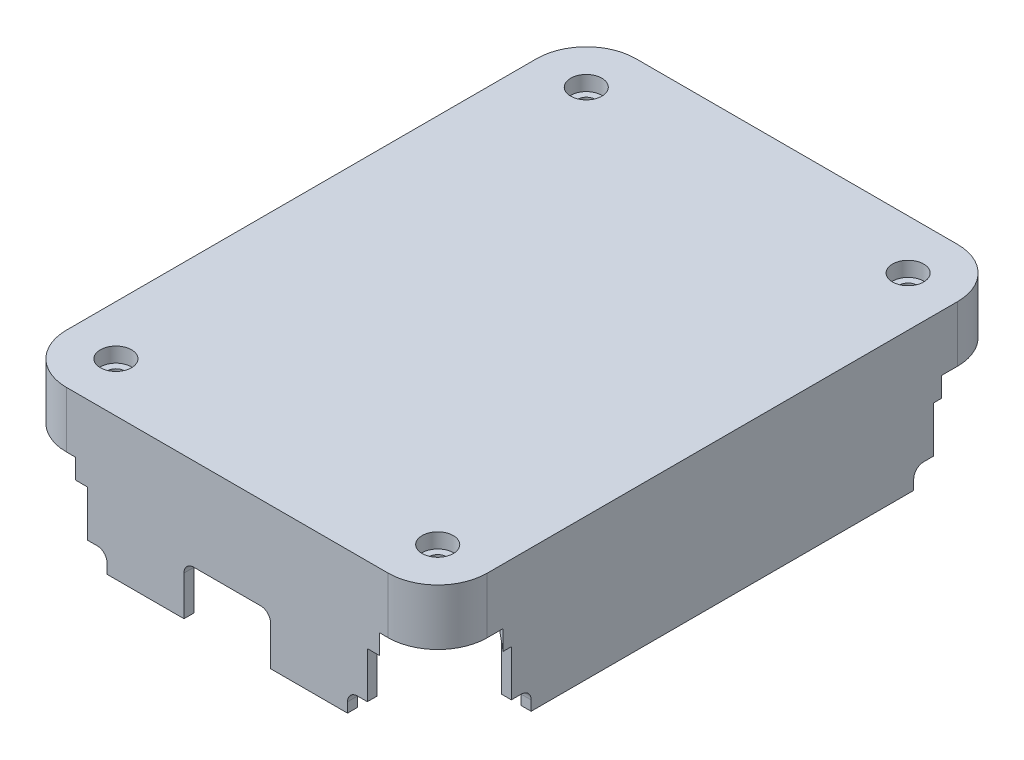
SolidWorks part; units mm, degrees
note: '?' marks a value the reader was unsure of.
material "3-D Printed ABS"
ref_plane "Front Plane" through (0, 0, 0) normal (0, 0, 1) x (1, 0, 0)
ref_plane "Top Plane" through (0, 0, 0) normal (0, 1, 0) x (1, 0, 0)
ref_plane "Right Plane" through (0, 0, 0) normal (1, 0, 0) x (0, 0, -1)
sketch "Sketch1" plane through (0, 0, 0) normal (0, 1, 0) x (1, 0, 0)
  line L1 (-53.975, -73.025) -> (53.975, -73.025)
  line L2 (-53.975, -73.025) -> (-53.975, 73.025)
  line L3 (-53.975, 73.025) -> (53.975, 73.025)
  line L4 (53.975, -73.025) -> (53.975, 73.025)
  line L5 (-53.975, -73.025) -> (53.975, 73.025) construction
  line L6 (-53.975, 73.025) -> (53.975, -73.025) construction
  point P0 (0, 0)
  dimension "D1" = 107.95
  dimension "D2" = 146.05
extrude "Boss-Extrude1" add sketch "Sketch1" against normal blind 2.54
sketch "Sketch13" plane through (0, 0, 0) normal (0, 1, 0) x (1, 0, 0)
  line L0 (0, 155.0212) -> (0, -155.0212) construction
  line L1 (0, 0) -> (-92.0171, 0) construction
  line L2 (53.975, -73.025) -> (53.975, 73.025) construction
  line L3 (53.975, -73.025) -> (28.575, -73.025)
  line L4 (53.975, -73.025) -> (53.975, -47.625)
  line L5 (53.975, -47.625) -> (28.575, -47.625)
  line L6 (28.575, -73.025) -> (28.575, -47.625)
  line L7 (-53.975, -73.025) -> (53.975, -73.025) construction
  line L8 (-28.575, -73.025) -> (-28.575, -47.625)
  line L9 (-53.975, -47.625) -> (-28.575, -47.625)
  line L10 (-53.975, -73.025) -> (-53.975, -47.625)
  line L11 (-53.975, -73.025) -> (-28.575, -73.025)
  line L12 (-53.975, 73.025) -> (-28.575, 73.025)
  line L13 (-53.975, 73.025) -> (-53.975, 47.625)
  line L14 (-53.975, 47.625) -> (-28.575, 47.625)
  line L15 (-28.575, 73.025) -> (-28.575, 47.625)
  line L16 (28.575, 73.025) -> (28.575, 47.625)
  line L17 (53.975, 47.625) -> (28.575, 47.625)
  line L18 (53.975, 73.025) -> (53.975, 47.625)
  line L19 (53.975, 73.025) -> (28.575, 73.025)
  dimension "D1" = 25.4
  dimension "D2" = 25.4
extrude "Boss-Extrude4" add sketch "Sketch13" against normal blind 19.431
sketch "Sketch2" plane through (0, 0, 0) normal (0, 1, 0) x (1, 0, 0)
  line L0 (0, 0) -> (100.1618, 0) construction
  line L1 (0, 0) -> (0, 86.3534) construction
  line L2 (-53.975, 73.025) -> (-53.975, -73.025) construction
  line L3 (53.975, 73.025) -> (-53.975, 73.025) construction
  line L4 (0, 0) -> (-53.975, 73.025) construction
  circle A0 centre (-41.275, 60.325) radius 3.302
  circle A1 centre (41.275, 60.325) radius 3.302
  circle A2 centre (41.275, -60.325) radius 3.302
  circle A3 centre (-41.275, -60.325) radius 3.302
  dimension "D1" = 6.604
  dimension "D3" = 12.7
  dimension "D2" = 12.7
extrude "Cut-Extrude1" cut sketch "Sketch2" against normal through all
sketch "Sketch3" plane through (0, 0, 0) normal (0, 1, 0) x (1, 0, 0)
  line L0 (-53.975, 25.4) -> (53.975, 25.4) construction
  line L1 (-23.495, 60.325) -> (-19.05, 60.325)
  line L2 (-23.495, 60.325) -> (-23.495, 44.45)
  line L3 (-23.495, 44.45) -> (-19.05, 44.45)
  line L4 (-19.05, 60.325) -> (-19.05, 44.45)
  line L5 (19.05, 60.325) -> (19.05, 44.45)
  line L6 (23.495, 44.45) -> (19.05, 44.45)
  line L7 (23.495, 60.325) -> (23.495, 44.45)
  line L8 (23.495, 60.325) -> (19.05, 60.325)
  line L9 (-53.975, 73.025) -> (-53.975, -73.025) construction
  line L10 (53.975, -73.025) -> (53.975, 73.025) construction
  line L11 (0, 0) -> (0, 97.7255) construction
  line L12 (0, 50.8) -> (0, -46.9255) construction
  line L13 (23.495, -9.525) -> (19.05, -9.525)
  line L14 (23.495, -9.525) -> (23.495, 6.35)
  line L15 (23.495, 6.35) -> (19.05, 6.35)
  line L16 (19.05, -9.525) -> (19.05, 6.35)
  line L17 (-19.05, -9.525) -> (-19.05, 6.35)
  line L18 (-23.495, 6.35) -> (-19.05, 6.35)
  line L19 (-23.495, -9.525) -> (-23.495, 6.35)
  line L20 (-23.495, -9.525) -> (-19.05, -9.525)
  dimension "D1" = 15.875
  dimension "D2" = 4.445
  dimension "D3" = 19.05
  dimension "D4" = 25.4
  dimension "D5" = 44.45
extrude "Cut-Extrude2" [suppressed] cut sketch "Sketch3" against normal through all
fillet "Fillet1" radius 12.7 4 edges at (53.975, -9.7155, -73.025) (53.975, -9.7155, 73.025) (-53.975, -9.7155, 73.025) (-53.975, -9.7155, -73.025)
sketch "Sketch4" plane through (0, 0, 0) normal (0, 1, 0) x (1, 0, 0)
  line L0 (0, 0) -> (80.9727, -80.9727) construction
  line L1 (0, 0) -> (-80.9727, -80.9727) construction
  line L2 (69.1118, -51.1513) -> (28.7006, -10.7401)
  line L3 (28.7006, -10.7401) -> (10.7401, -28.7006)
  line L4 (10.7401, -28.7006) -> (51.1513, -69.1118)
  line L5 (51.1513, -69.1118) -> (69.1118, -51.1513)
  line L6 (0, 0) -> (0, -118.7381) construction
  line L7 (0, 0) -> (-98.4177, 0) construction
  line L8 (-51.1513, -69.1118) -> (-69.1118, -51.1513)
  line L9 (-69.1118, -51.1513) -> (-28.7006, -10.7401)
  line L10 (-28.7006, -10.7401) -> (-10.7401, -28.7006)
  line L11 (-10.7401, -28.7006) -> (-51.1513, -69.1118)
  line L12 (-69.1118, 51.1513) -> (-28.7006, 10.7401)
  line L13 (-51.1513, 69.1118) -> (-69.1118, 51.1513)
  line L14 (-10.7401, 28.7006) -> (-51.1513, 69.1118)
  line L15 (-28.7006, 10.7401) -> (-10.7401, 28.7006)
  line L16 (51.1513, 69.1118) -> (69.1118, 51.1513)
  line L17 (69.1118, 51.1513) -> (28.7006, 10.7401)
  line L18 (28.7006, 10.7401) -> (10.7401, 28.7006)
  line L19 (10.7401, 28.7006) -> (51.1513, 69.1118)
  point P6 (19.7204, -19.7204)
  dimension "D1" = 25.4
  dimension "D2" = 57.15
  dimension "D3" = 45
extrude "Cut-Extrude3" [suppressed] cut sketch "Sketch4" against normal blind 1.5875
sketch "Sketch6" [suppressed] plane through (0, 0, 0) normal (0, 1, 0) x (1, 0, 0)
  line L0 (46.3377, -44.1074) -> (34.6634, -32.4331) construction
  line L1 (0, 0) -> (0, -117.7376) construction
  line L2 (0, 0) -> (-151.7285, 0) construction
  line L4 (28.1601, -10.1996) -> (10.1996, -28.1601) construction
  line L5 (50.6107, -68.5712) -> (68.5712, -50.6107) construction
  text T0 "ESC" font "Century Gothic" height in points 22
  dimension "D1" = 45
  dimension "D2" = 20.32
  dimension "D3" = 20.32
extrude "Cut-Extrude5" [suppressed] cut sketch "Sketch6" against normal blind 3.175
sketch "Sketch5" plane through (0, 0, 0) normal (0, 1, 0) x (1, 0, 0)
  line L0 (41.275, 73.025) -> (-41.275, 73.025) construction
  line L1 (14.2875, 15.875) -> (-14.2875, 15.875)
  line L2 (14.2875, 15.875) -> (14.2875, 66.675)
  line L3 (14.2875, 66.675) -> (-14.2875, 66.675)
  line L4 (-14.2875, 15.875) -> (-14.2875, 66.675)
  point P4 (0, 15.875)
  dimension "D1" = 50.8
  dimension "D2" = 28.575
  dimension "D3" = 6.35
extrude "Cut-Extrude4" [suppressed] cut sketch "Sketch5" against normal blind 1.5875
ref_axis "Axis1" through (0, 0.3175, 0) along (0, -1, 0)?
pattern_circular "CirPattern1" [suppressed] count 4 over 360 about axis through (0, 0.3175, 0) along (0, -1, 0)
sketch "Sketch7" plane through (0, 0, 0) normal (0, 1, 0) x (1, 0, 0)
  line L0 (0, 0) -> (0, -54.962) construction
  line L1 (63.4018, -13.3522) -> (38.0018, -13.3522)
  line L2 (63.4018, -13.3522) -> (63.4018, 43.7978)
  line L3 (63.4018, 43.7978) -> (38.0018, 43.7978)
  line L4 (38.0018, -13.3522) -> (38.0018, 43.7978)
  line L5 (-38.0018, -13.3522) -> (-38.0018, 43.7978)
  line L6 (-63.4018, 43.7978) -> (-38.0018, 43.7978)
  line L7 (-63.4018, -13.3522) -> (-63.4018, 43.7978)
  line L8 (-63.4018, -13.3522) -> (-38.0018, -13.3522)
  line L9 (-41.275, -73.025) -> (41.275, -73.025) construction
  line L10 (38.5677, -40.64) -> (-18.5823, -40.64)
  line L11 (38.5677, -40.64) -> (38.5677, -66.04)
  line L12 (38.5677, -66.04) -> (-18.5823, -66.04)
  line L13 (-18.5823, -40.64) -> (-18.5823, -66.04)
  line L14 (38.5677, -40.64) -> (-18.5823, -66.04) construction
  line L15 (38.5677, -66.04) -> (-18.5823, -40.64) construction
  line L16 (19.844, -36.1003) -> (-37.306, -36.1003)
  line L17 (19.844, -36.1003) -> (19.844, -61.5003)
  line L18 (19.844, -61.5003) -> (-37.306, -61.5003)
  line L19 (-37.306, -36.1003) -> (-37.306, -61.5003)
  line L20 (19.844, -36.1003) -> (-37.306, -61.5003) construction
  line L21 (19.844, -61.5003) -> (-37.306, -36.1003) construction
  point P11 (9.9927, -53.34)
  point P18 (-8.731, -48.8003)
  dimension "D1" = 57.15
  dimension "D2" = 25.4
  dimension "D3" = 57.15
  dimension "D4" = 25.4
  dimension "D5" = 6.985
  dimension "D6" = 57.15
  dimension "D7" = 25.4
extrude "Cut-Extrude6" [suppressed] cut sketch "Sketch7" against normal blind 1.27
sketch "Sketch8" plane through (0, 0, 0) normal (0, 1, 0) x (1, 0, 0)
  line L7 (19.05, -31.75) -> (-19.05, -31.75)
  line L8 (19.05, -31.75) -> (19.05, 31.75)
  line L9 (19.05, 31.75) -> (-19.05, 31.75)
  line L10 (-19.05, -31.75) -> (-19.05, 31.75)
  point P0 (0, 0)
  dimension "D1" = 38.1
  dimension "D2" = 31.75
  dimension "D3" = 63.5
extrude "Boss-Extrude3" [suppressed] add sketch "Sketch8" along normal blind 2.54
sketch "Sketch11" plane through (0, 0, 0) normal (0, 1, 0) x (1, 0, 0)
  line L1 (19.05, -9.525) -> (-19.05, -9.525)
  line L2 (19.05, -9.525) -> (19.05, 6.35)
  line L3 (19.05, 6.35) -> (-19.05, 6.35)
  line L4 (-19.05, -9.525) -> (-19.05, 6.35)
extrude "Cut-Extrude9" [suppressed] cut sketch "Sketch11" against normal mid plane 2.54
sketch "Sketch12" [suppressed] plane through (0, 0, 0) normal (0, 1, 0) x (1, 0, 0)
  line L0 (-23.495, -9.525) -> (-19.05, -9.525) construction
  line L1 (12.7, -9.525) -> (-12.7, -9.525)
  line L2 (12.7, -9.525) -> (12.7, 6.35)
  line L3 (12.7, 6.35) -> (-12.7, 6.35)
  line L4 (-12.7, -9.525) -> (-12.7, 6.35)
  line L5 (-19.05, 6.35) -> (-23.495, 6.35) construction
  line L6 (19.05, 52.3875) -> (-19.05, 52.3875) construction
  line L7 (19.05, 60.325) -> (19.05, 44.45) construction
  line L8 (-19.05, 44.45) -> (-19.05, 60.325) construction
  line L9 (-12.7, 114.3) -> (-12.7, 98.425)
  line L10 (12.7, 98.425) -> (-12.7, 98.425)
  line L11 (12.7, 114.3) -> (12.7, 98.425)
  line L12 (12.7, 114.3) -> (-12.7, 114.3)
  point P8 (0, -9.525)
  dimension "D1" = 25.4
extrude "Cut-Extrude12" [suppressed] cut sketch "Sketch12" along normal through all
sketch "Sketch9" plane through (0, 0, 0) normal (0, 1, 0) x (1, 0, 0)
  line L1 (25.1579, -52.4084) -> (-25.6421, -52.4084)
  line L2 (25.1579, -52.4084) -> (25.1579, -1.6084)
  line L3 (25.1579, -1.6084) -> (-25.6421, -1.6084)
  line L4 (-25.6421, -52.4084) -> (-25.6421, -1.6084)
  line L5 (25.1579, -52.4084) -> (-25.6421, -1.6084) construction
  line L6 (25.1579, -1.6084) -> (-25.6421, -52.4084) construction
  point P0 (-0.2421, -27.0084)
  dimension "D1" = 50.8
  dimension "D2" = 50.8
fillet "Fillet2" [suppressed] radius 12.7
sketch "Sketch14" plane through (0, -19.431, 0) normal (0, -1, 0) x (1, 0, 0)
  line L0 (0, 0) -> (0, -152.4) construction
  line L1 (0, 0) -> (152.4, 0) construction
  line L2 (0, 0) -> (152.4, -152.4) construction
  line L3 (152.4, -152.4) -> (41.275, -60.325) construction
  line L4 (41.275, -60.325) -> (27.042, -48.5319) construction
  line L5 (27.042, -48.5319) -> (0, -26.1257) construction
  line L6 (20.692, -28.6742) -> (6.35, -45.9835)
  line L7 (6.35, -45.9835) -> (139.337, -156.1727)
  line L8 (139.337, -156.1727) -> (153.679, -138.8634)
  line L9 (153.679, -138.8634) -> (20.692, -28.6742)
  line L10 (-20.692, -28.6742) -> (-6.35, -45.9835)
  line L11 (-153.679, -138.8634) -> (-20.692, -28.6742)
  line L12 (-6.35, -45.9835) -> (-139.337, -156.1727)
  line L13 (-139.337, -156.1727) -> (-153.679, -138.8634)
  line L14 (-153.679, 138.8634) -> (-20.692, 28.6742)
  line L15 (-139.337, 156.1727) -> (-153.679, 138.8634)
  line L16 (-6.35, 45.9835) -> (-139.337, 156.1727)
  line L17 (-20.692, 28.6742) -> (-6.35, 45.9835)
  line L18 (20.692, 28.6742) -> (6.35, 45.9835)
  line L19 (139.337, 156.1727) -> (153.679, 138.8634)
  line L20 (153.679, 138.8634) -> (20.692, 28.6742)
  line L21 (6.35, 45.9835) -> (139.337, 156.1727)
  point P3 (13.521, -37.3288)
  point P6 (41.275, -60.325)
  dimension "D1" = 152.4
  dimension "D2" = 152.4
  dimension "D3" = 6.35
  dimension "D4" = 11.2395
extrude "Cut-Extrude13" cut sketch "Sketch14" against normal blind 5.08
sketch "Sketch15" plane through (0, 0, 0) normal (0, 1, 0) x (1, 0, 0)
  line L0 (0, 0) -> (72.5178, 0) construction
  line L1 (0, 0) -> (0, 124.598) construction
  circle A0 centre (-41.275, 60.325) radius 6.35
  circle A1 centre (41.275, 60.325) radius 6.35
  circle A2 centre (-41.275, -60.325) radius 6.35
  circle A3 centre (41.275, -60.325) radius 6.35
extrude "Boss-Extrude5" add sketch "Sketch15" against normal offset from surface (11.811 mm away) 2.54 up to face at (-41.6508, -14.351, -60.7008)
hole_wizard "M4 Clearance Hole1" [suppressed] positions "Sketch18" profile "Sketch16" hole size "M4" standard "ANSI Metric"
sketch "Sketch18" plane through (0, -19.05, 0) normal (0, -1, 0) x (-1, 0, 0)
  point P0 (41.275, 60.325)
  point P3 (41.275, -60.325)
  point P6 (-41.275, -60.325)
  point P9 (-41.275, 60.325)
sketch "Sketch16" plane through (-41.275, -19.05, -60.325) normal (1, 0, 0) x (0, 0, -1)
  line L0 (0, 0) -> (0, 19.05)
  line L1 (0, 19.05) -> (2.25, 19.05)
  line L2 (2.25, 19.05) -> (2.25, 0)
  line L5 (2.25, 0) -> (0, 0)
  line L11 (0, -6.35) -> (0, 107.95) construction
  dimension "Thru Hole Dia." = 4.5
  dimension "Thru Hole Depth" = 19.05
hole_wizard "CBORE for M4 SHCS1" [suppressed] positions "Sketch21" profile "Sketch20" counterbore size "M4" standard "ANSI Metric"
sketch "Sketch21" [suppressed] plane through (0, 0, 0) normal (0, 1, 0) x (1, 0, 0)
  point P0 (41.275, 60.325)
  point P3 (-41.275, 60.325)
  point P6 (-41.275, -60.325)
  point P9 (41.275, -60.325)
sketch "Sketch20" plane through (41.275, 0, -60.325) normal (1, 0, 0) x (0, 0, 1)
  line L0 (0, 0) -> (0, 24.13)
  line L1 (0, 24.13) -> (2.25, 24.13)
  line L3 (2.25, 24.13) -> (2.25, 4)
  line L4 (2.25, 4) -> (4, 4)
  line L5 (4, 4) -> (4, 0)
  line L7 (4, 0) -> (0, 0)
  line L11 (0, -6.35) -> (0, 107.95) construction
  dimension "Thru Hole Dia." = 4.5
  dimension "Thru Hole Depth" = 24.13
  dimension "C'Bore Dia." = 8
  dimension "C'Bore Depth" = 4
sketch "Sketch23" plane through (0, -14.351, 0) normal (0, -1, 0) x (1, 0, 0)
  circle A0 centre (-41.275, -60.325) radius 2.25
  dimension "D1" = 4.5
extrude "Cut-Extrude14" cut sketch "Sketch23" against normal through all
sketch "Sketch24" plane through (0, 0, 0) normal (0, 1, 0) x (1, 0, 0)
  circle A0 centre (-41.275, 60.325) radius 4
  dimension "D1" = 8
extrude "Cut-Extrude15" cut sketch "Sketch24" against normal blind 3.81
mirror "Mirror1" about plane through (0, 0, 0) normal (0, 0, 1) of "Cut-Extrude15", "Cut-Extrude14"
mirror "Mirror2" about plane through (0, 0, 0) normal (1, 0, 0) of "Cut-Extrude15", "Cut-Extrude14", "Mirror1"
fillet "Fillet3" radius 12.7 4 edges at (-28.575, -8.4455, -47.625) (28.575, -8.4455, -47.625) (28.575, -8.4455, 47.625) (-28.575, -8.4455, 47.625)
sketch "Sketch25" plane through (0, 0, 0) normal (0, 1, 0) x (1, 0, 0)
  line L0 (0, 0) -> (0, -33.9706) construction
  line L1 (0, 0) -> (63.8751, 0) construction
  circle A0 centre (30.0609, 0) radius 3.4925
  circle A1 centre (30.0609, -24.9682) radius 3.4925
  circle A2 centre (30.0609, 24.9682) radius 3.4925
  circle A3 centre (-30.0609, 24.9682) radius 3.4925
  circle A4 centre (-30.0609, -24.9682) radius 3.4925
  circle A5 centre (-30.0609, 0) radius 3.4925
  dimension "D1" = 6.985
  dimension "D2" = 6.985
  dimension "D3" = 24.9682
  dimension "D4" = 30.0609
extrude "GimbalMount1" [suppressed] cut sketch "Sketch25" against normal through all
sketch "Sketch26" [suppressed] plane through (0, 0, 0) normal (0, 1, 0) x (1, 0, 0)
  circle A0 centre (30.0609, -24.9682) radius 5.715
  circle A1 centre (30.0609, 0) radius 5.715
  circle A2 centre (30.0609, 24.9682) radius 5.715
  circle A3 centre (-30.0609, -24.9682) radius 5.715
  circle A4 centre (-30.0609, 0) radius 5.715
  circle A5 centre (-30.0609, 24.9682) radius 5.715
  dimension "D1" = 11.43
extrude "GimbalMount2" [suppressed] cut sketch "Sketch26" against normal blind 1.524
fillet "Fillet4" radius 1.016 4 edges at (41.275, -14.351, 63.627) (-41.275, -14.351, 57.023) (-41.275, -14.351, -57.023) (41.275, -14.351, -63.627)
sketch "Sketch27" plane through (0, -2.54, 0) normal (0, -1, 0) x (1, 0, 0)
  line L1 (35.9208, -73.025) -> (-35.9208, -73.025)
  line L2 (35.9208, -73.025) -> (35.9208, -70.485)
  line L3 (35.9208, -70.485) -> (-35.9208, -70.485)
  line L4 (-35.9208, -73.025) -> (-35.9208, -70.485)
  line L6 (0, 0) -> (0, -45.0707) construction
  line L7 (0, 0) -> (-77.1364, 0) construction
  line L8 (-35.9208, 73.025) -> (-35.9208, 70.485)
  line L9 (35.9208, 70.485) -> (-35.9208, 70.485)
  line L10 (35.9208, 73.025) -> (35.9208, 70.485)
  line L11 (35.9208, 73.025) -> (-35.9208, 73.025)
  line L13 (53.975, -54.1469) -> (51.435, -54.1469)
  line L14 (53.975, -54.1469) -> (53.975, 54.1469)
  line L15 (53.975, 54.1469) -> (51.435, 54.1469)
  line L16 (51.435, -54.1469) -> (51.435, 54.1469)
  line L17 (-51.435, -54.1469) -> (-51.435, 54.1469)
  line L18 (-53.975, 54.1469) -> (-51.435, 54.1469)
  line L19 (-53.975, -54.1469) -> (-53.975, 54.1469)
  line L20 (-53.975, -54.1469) -> (-51.435, -54.1469)
  line L22 (28.575, -64.3985) -> (38.9863, -73.025) construction
  line L23 (-38.9863, -73.025) -> (-28.575, -64.3985) construction
  line L24 (28.575, -73.025) -> (-28.575, -73.025) construction
  line L25 (53.975, -56.2515) -> (43.5637, -47.625) construction
  line L26 (53.975, 47.625) -> (53.975, -47.625) construction
  line L27 (43.5637, 47.625) -> (53.975, 56.2515) construction
  dimension "D1" = 2.54
  dimension "D2" = 2.54
extrude "Boss-Extrude6" add sketch "Sketch27" along normal blind 33.782
sketch "Sketch28" plane through (0, 0, -73.025) normal (0, 0, -1) x (-1, 0, 0)
  line L0 (-41.275, 0) -> (41.275, 0) construction
  line L1 (-17.526, -36.322) -> (17.526, -36.322)
  line L2 (-16.891, -28.702) -> (-16.891, -21.3995)
  line L3 (-14.351, -18.8595) -> (14.351, -18.8595)
  line L4 (16.891, -28.702) -> (16.891, -21.3995)
  line L5 (35.9208, -36.322) -> (-35.9208, -36.322) construction
  line L6 (19.431, -31.242) -> (27.051, -31.242)
  line L7 (0, -18.8595) -> (0, 0) construction
  line L8 (17.526, -36.322) -> (29.591, -36.322)
  line L9 (29.591, -33.782) -> (29.591, -36.322)
  line L11 (-19.431, -31.242) -> (-27.051, -31.242)
  line L13 (-17.526, -36.322) -> (-29.591, -36.322)
  line L14 (-29.591, -33.782) -> (-29.591, -36.322)
  arc A0 (-29.591, -33.782) -> (-27.051, -31.242) centre (-27.051, -33.782) cw
  arc A1 (-19.431, -31.242) -> (-16.891, -28.702) centre (-19.431, -28.702) ccw
  arc A2 (-16.891, -21.3995) -> (-14.351, -18.8595) centre (-14.351, -21.3995) cw
  arc A3 (14.351, -18.8595) -> (16.891, -21.3995) centre (14.351, -21.3995) cw
  arc A4 (16.891, -28.702) -> (19.431, -31.242) centre (19.431, -28.702) ccw
  arc A5 (27.051, -31.242) -> (29.591, -33.782) centre (27.051, -33.782) cw
  point P5 (0, -36.322)
  point P19 (-29.591, -31.242)
  point P25 (-16.891, -18.8595)
  point P28 (16.891, -18.8595)
  point P34 (29.591, -31.242)
  dimension "D7" = 2.54
  dimension "D1" = 17.4625
  dimension "D2" = 33.782
  dimension "D3" = 10.16
  dimension "D4" = 5.08
  dimension "D5" = 10.16
  dimension "D6" = 5.08
extrude "Cut-Extrude16" cut sketch "Sketch28" against normal blind 41.656
sketch "Sketch29" plane through (-53.975, 0, 0) normal (-1, 0, 0) x (0, 0, 1)
  line L0 (0, -36.322) -> (0, -17.4257) construction
  line L1 (-54.1469, -36.322) -> (-49.0669, -36.322)
  line L2 (-54.1469, -36.322) -> (-54.1469, -31.242)
  line L3 (-54.1469, -31.242) -> (-51.6069, -31.242)
  line L4 (-49.0669, -36.322) -> (-49.0669, -33.782)
  line L5 (54.1469, -36.322) -> (-54.1469, -36.322) construction
  line L6 (49.0669, -36.322) -> (49.0669, -33.782)
  line L7 (54.1469, -31.242) -> (51.6069, -31.242)
  line L8 (54.1469, -36.322) -> (54.1469, -31.242)
  line L9 (54.1469, -36.322) -> (49.0669, -36.322)
  arc A0 (-49.0669, -33.782) -> (-51.6069, -31.242) centre (-51.6069, -33.782) ccw
  arc A1 (49.0669, -33.782) -> (51.6069, -31.242) centre (51.6069, -33.782) cw
  dimension "D1" = 2.54
  dimension "D2" = 5.08
  dimension "D3" = 5.08
extrude "Cut-Extrude17" cut sketch "Sketch29" against normal through all
sketch "Sketch30" plane through (0, 0, 73.025) normal (0, 0, 1) x (1, 0, 0)
  line L0 (0, -36.322) -> (0, -22.969) construction
  line L1 (-35.9208, -36.322) -> (-30.8408, -36.322)
  line L2 (-35.9208, -36.322) -> (-35.9208, -31.242)
  line L3 (-35.9208, -31.242) -> (-33.3808, -31.242)
  line L4 (-30.8408, -36.322) -> (-30.8408, -33.782)
  line L5 (35.9208, -36.322) -> (-35.9208, -36.322) construction
  line L6 (30.8408, -36.322) -> (30.8408, -33.782)
  line L7 (35.9208, -31.242) -> (33.3808, -31.242)
  line L8 (35.9208, -36.322) -> (35.9208, -31.242)
  line L9 (35.9208, -36.322) -> (30.8408, -36.322)
  arc A0 (-30.8408, -33.782) -> (-33.3808, -31.242) centre (-33.3808, -33.782) ccw
  arc A1 (30.8408, -33.782) -> (33.3808, -31.242) centre (33.3808, -33.782) cw
  dimension "D1" = 2.54
  dimension "D2" = 5.08
  dimension "D3" = 5.08
extrude "Cut-Extrude18" cut sketch "Sketch30" against normal through all
sketch "Sketch31" plane through (0, 0, 73.025) normal (0, 0, 1) x (1, 0, 0)
  line L0 (30.8408, -36.322) -> (-30.8408, -36.322) construction
  line L1 (-11.1125, -36.322) -> (11.1125, -36.322)
  line L2 (-11.1125, -36.322) -> (-11.1125, -23.622)
  line L3 (-11.1125, -23.622) -> (11.1125, -23.622)
  line L4 (11.1125, -36.322) -> (11.1125, -23.622)
  line L5 (0, -23.622) -> (0, -15.4197) construction
  line L6 (-41.275, 0) -> (41.275, 0) construction
  point P10 (0, 0)
  dimension "D1" = 12.7
  dimension "D2" = 22.225
extrude "Cut-Extrude19" cut sketch "Sketch31" against normal up to next
fillet "Fillet5" radius 2.54 2 edges at (11.1125, -23.622, 71.755) (-11.1125, -23.622, 71.755)
equation "\"Plate Thickness\"= \"Plate Thickness@Quad Assemb.sldasm\""
equation "\"D1@Boss-Extrude1\"=\"Plate Thickness\""
equation "\"Plate Dim X\"= \"Plate Dim X@Quad Assemb.sldasm\""
equation "\"Plate Dim Y\"= \"Plate Dim Y@Quad Assemb.sldasm\""
equation "\"D1@Boss-Extrude4\"=\"Component Y@Quad Assemb.sldasm\"-\"ArmBase@Arm V3-1.Part\""
equation "\"D4@Sketch14\"=\"ArmBase@Arm V3-1.Part\"/2+.005"
equation "\"Dowell Width\"= \"Dowell Width@Quad Assemb.sldasm\""
equation "\"D1@Sketch2\"=\"Dowell Width\"+.01"
equation "\"Dowell Height\"= \"Dowell Height@Quad Assemb.sldasm\""
equation "\"D1@Boss-Extrude5\"=\"Dowell Height\""
equation "\"GimbalMount1\"= if ( \"Gimbal Mount@Quad Assemb.sldasm\" = 1 , \"unsuppressed\" , \"suppressed\" )"
equation "\"GimbalMount2\"= if ( \"Gimbal Mount@Quad Assemb.sldasm\" = 1 , \"unsuppressed\" , \"suppressed\" )"
equation "\"D1@Boss-Extrude6\"=\"Component Y@Quad Assemb.sldasm\"-.31"
equation "\"D1@Sketch28\"=\"radio rx Z@Quad Assemb.sldasm\"+3/16"
equation "\"D2@Sketch28\"=\"radio rx x@quad assemb.sldasm\"+.2"
